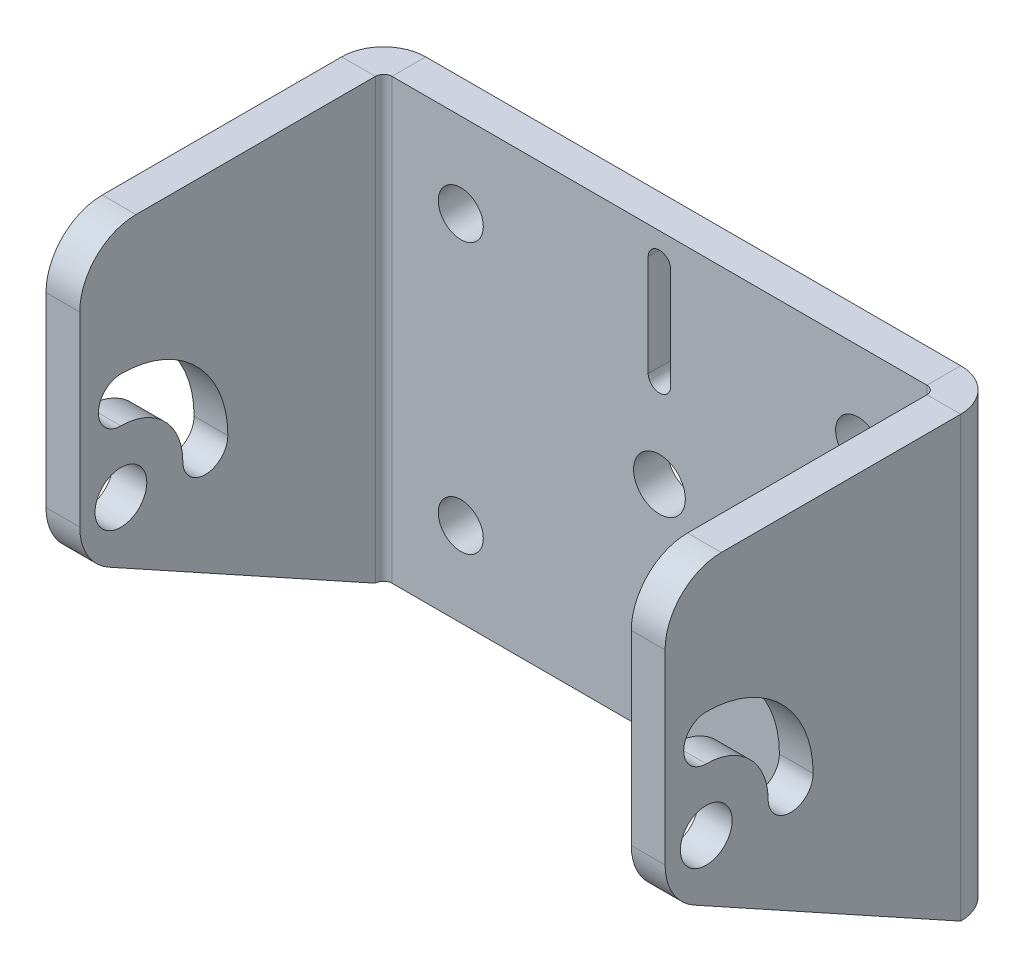
SolidWorks part; units mm, degrees
note: The reader was unsure of these and kept them because the rebuilt part matched: flange length of "Aresta-Flange1".
ref_plane "Plano frontal" through (0, 0, 0) normal (0, 0, 1) x (1, 0, 0)
ref_plane "Plano superior" through (0, 0, 0) normal (0, 1, 0) x (1, 0, 0)
ref_plane "Plano direito" through (0, 0, 0) normal (1, 0, 0) x (0, 0, -1)
sketch "Esboço1" plane through (0, 0, 0) normal (0, 0, 1) x (1, 0, 0)
  line L1 (-22.0063, 15.0091) -> (26.9937, 15.0091)
  line L2 (-22.0063, 15.0091) -> (-22.0063, -23.9909)
  line L3 (-22.0063, -23.9909) -> (26.9937, -23.9909)
  line L4 (26.9937, 15.0091) -> (26.9937, -23.9909)
  dimension "D1" = 49
  dimension "D2" = 39
base flange "Flange-base1" sketch "Esboço1" thickness 3 reverse thickness direction no parameters "D1"=0.7366
sketch "Esboço6" plane through (0, 0, 0) normal (0, 0, 1) x (1, 0, 0)
  line L1 (-15.1563, 7.5091) -> (20.1437, 7.5091)
  line L2 (-15.1563, 7.5091) -> (-15.1563, -16.4909)
  line L3 (-15.1563, -16.4909) -> (20.1437, -16.4909)
  line L4 (20.1437, 7.5091) -> (20.1437, -16.4909)
  line L6 (26.9937, 15.0091) -> (-22.0063, 15.0091) construction
  line L7 (-22.0063, -23.9909) -> (26.9937, -23.9909) construction
  line L8 (2.4937, 15.0091) -> (2.4937, -23.9909) construction
  line L9 (2.4937, 3.5238) -> (2.4937, 12.5238) construction
  line L10 (1.4937, 3.5238) -> (1.4937, 12.5238)
  line L11 (3.4937, 3.5238) -> (3.4937, 12.5238)
  line L12 (-22.0063, -4.4909) -> (26.9937, -4.4909) construction
  line L13 (-22.0063, 15.0091) -> (-22.0063, -23.9909) construction
  line L14 (26.9937, -23.9909) -> (26.9937, 15.0091) construction
  line L15 (2.4937, -12.5057) -> (2.4937, -21.5057) construction
  line L16 (1.4937, -12.5057) -> (1.4937, -21.5057)
  line L17 (3.4937, -12.5057) -> (3.4937, -21.5057)
  circle A0 centre (-15.1563, 7.5091) radius 2
  circle A1 centre (-15.1563, -16.4909) radius 2
  circle A2 centre (20.1437, -16.4909) radius 2
  circle A3 centre (20.1437, 7.5091) radius 2
  circle A4 centre (2.4937, -4.4909) radius 2.3
  arc A5 (1.4937, 3.5238) -> (3.4937, 3.5238) centre (2.4937, 3.5238) ccw
  arc A6 (3.4937, 12.5238) -> (1.4937, 12.5238) centre (2.4937, 12.5238) ccw
  arc A7 (1.4937, -12.5057) -> (3.4937, -12.5057) centre (2.4937, -12.5057) cw
  arc A8 (3.4937, -21.5057) -> (1.4937, -21.5057) centre (2.4937, -21.5057) cw
  point P18 (2.4937, 8.0238)
  point P31 (2.4937, -17.0057)
  dimension "D1" = 6.85
  dimension "D3" = 7.5
  dimension "D4" = 7.5
extrude "Corte-extrusão1" cut sketch "Esboço6" against normal blind 10 contours L1 A0 L2 | L2 A0 L1 | L2 A1 L3 | L3 A1 L2 | A4 | L10 A5 L11 L1 | L11 A6 L10 L1 | A7 L16 L3 L17 | A8 L17 L3 L16 | A2 L3 L4 | A2 L4 L3 | A3 L4 L1 | A3 L1 L4 normal cut yes
edge flange "Aresta-Flange1" sketch "Esboço11" flange profiles "Esboço11", "Esboço12" flange angle 90 flange length 30 flange position material outside bend radius 0.7366 thickness 3 parameters "D6"=10, "D8"=1
sketch "Esboço11" plane through (26.9937, 0, 0) normal (1, 0, 0) x (0, 1, 0)
  line L0 (-23.9909, 0) -> (15.0091, 0) construction
  line L1 (-23.9909, 0) -> (15.0091, 0)
  line L2 (-23.9909, 0) -> (-23.9909, 27)
  line L3 (-23.9909, 27) -> (15.0091, 27)
  line L4 (15.0091, 27) -> (15.0091, 0)
sketch "Esboço12" plane through (-22.0063, 0, 0) normal (-1, 0, 0) x (0, -1, 0)
  line L0 (-15.0091, 0) -> (23.9909, 0) construction
  line L1 (-15.0091, 0) -> (23.9909, 0)
  line L2 (-15.0091, 0) -> (-15.0091, 27)
  line L3 (-15.0091, 27) -> (23.9909, 27)
  line L4 (23.9909, 27) -> (23.9909, 0)
bend "DobradeAresta1" bend radius 0.7366 bend angle 90 parameters "D5"=1
bend "DobradeAresta2" bend radius 0.7366 bend angle 90 parameters "D5"=2
sketch "Esboço13" plane through (-25.0063, 0, 0) normal (-1, 0, 0) x (0, 0, 1)
  line L0 (0.7366, -23.9909) -> (27, -9.4909) construction
  line L1 (27, -23.9909) -> (27, 15.0091) construction
  line L2 (27, -9.4909) -> (0.7366, 15.0091) construction
  line L3 (0.7366, -23.9909) -> (27, -23.9909)
  line L4 (27, -23.9909) -> (27, -9.4909)
  line L5 (27, -9.4909) -> (0.7366, -23.9909)
  circle A0 centre (23.3439, -6.0803) radius 2.3
  arc A1 (23.3439, 1.4197) -> (15.8439, -6.0803) centre (23.3439, -6.0803) ccw construction
  arc A6 (23.3439, 3.4197) -> (13.8439, -6.0803) centre (23.3439, -6.0803) ccw
  arc A7 (23.3439, -0.5803) -> (17.8439, -6.0803) centre (23.3439, -6.0803) ccw
  arc A8 (23.3439, -0.5803) -> (23.3439, 3.4197) centre (23.3439, 1.4197) ccw
  arc A9 (13.8439, -6.0803) -> (17.8439, -6.0803) centre (15.8439, -6.0803) ccw
  point P12 (18.0406, -0.777)
  dimension "D3" = 4.6
  dimension "D4" = 3.6561
  dimension "D6" = 4
  dimension "D1" = 14.5
  dimension "D2" = 5
  dimension "D7" = 7.5
extrude "Corte-extrusão2" cut sketch "Esboço13" against normal blind 70 normal cut yes
fillet "Filete1" radius 5 4 edges at (28.4937, -9.4909, 27) (28.4937, 15.0091, 27) (-23.5063, -9.4909, 27) (-23.5063, 15.0091, 27)
sketch "Curva-Linhas1" [suppressed] plane through (0, 0, 0) normal (0, 1, 0) x (1, 0, 0)
sketch "Caixa delimitadora1" [suppressed] plane through (0, 0, 0) normal (0, 1, 0) x (1, 0, 0)
sheet metal parameters "Chapa metálica1" thickness 3 parameters "D1"=0.7366
flat pattern "Padrão-Plano1" [suppressed]
sketch "Curva-Linhas2" plane through (0, 0, 0) normal (0, 1, 0) x (1, 0, 0)
sketch3d "Caixa delimitadora2" [suppressed]
  line L0 (21.0063, -23.9909, 0) -> (-26.9937, -23.9909, 0) construction
  line L1 (21.0063, 15.0091, 0) -> (-26.9937, 15.0091, 0) construction
  line L2 (21.0063, -23.9909, 0) -> (21.0063, 15.0091, 0) construction
  line L3 (-26.9937, -23.9909, 0) -> (-26.9937, 15.0091, 0) construction
sheet metal parameters "Chapa metálica2" thickness 3 parameters "D1"=0.7366
flat pattern "Padrão-Plano1"
sketch "Curva-Linhas2" plane through (0, 0, 0) normal (0, 1, 0) x (1, 0, 0)
sketch3d "Caixa delimitadora2" [suppressed]
  line L0 (-21.0063, -23.9909, 0) -> (26.9937, -23.9909, 0) construction
  line L1 (-21.0063, 15.0091, 0) -> (26.9937, 15.0091, 0) construction
  line L2 (-21.0063, -23.9909, 0) -> (-21.0063, 15.0091, 0) construction
  line L3 (26.9937, -23.9909, 0) -> (26.9937, 15.0091, 0) construction
sheet metal parameters "Chapa metálica3" thickness 3 parameters "D1"=0.7366
flat pattern "Padrão-Plano1"
sketch "Curva-Linhas2" plane through (0, 0, 0) normal (0, 0, 1) x (1, 0, 0)
  line L0 (-22.0263, 15.0091) -> (-22.0263, -23.9909) construction
  line L1 (28.0138, -23.9909) -> (28.0138, 15.0091) construction
  line L2 (-22.0263, 15.0091) -> (-22.0263, -23.9909) construction
  line L3 (28.0138, -23.9909) -> (28.0138, 15.0091) construction
sketch3d "Caixa delimitadora2" [suppressed]
  line L0 (-50.0463, -23.9909, 0) -> (56.0338, -23.9909, 0) construction
  line L1 (-50.0463, 15.0091, 0) -> (56.0338, 15.0091, 0) construction
  line L2 (-50.0463, -23.9909, 0) -> (-50.0463, 15.0091, 0) construction
  line L3 (56.0338, -23.9909, 0) -> (56.0338, 15.0091, 0) construction
bend of the flat pattern "Planificar-<DobradeAresta1>1"
bend of the flat pattern "Planificar-<DobradeAresta2>1"
sheet metal parameters "Chapa metálica4" thickness 3 parameters "D1"=0.7366
flat pattern "Padrão-Plano1"
sketch "Curva-Linhas2" plane through (0, 0, 0) normal (0, 0, 1) x (1, 0, 0)
  line L0 (-23.0263, 15.0091) -> (-23.0263, -23.9909) construction
  line L1 (28.0138, -23.9909) -> (28.0138, 15.0091) construction
  line L2 (-23.0263, 15.0091) -> (-23.0263, -23.9909) construction
  line L3 (28.0138, -23.9909) -> (28.0138, 15.0091) construction
sketch3d "Caixa delimitadora2" [suppressed]
  line L0 (-51.0463, -23.9909, 0) -> (56.0338, -23.9909, 0) construction
  line L1 (-51.0463, 15.0091, 0) -> (56.0338, 15.0091, 0) construction
  line L2 (-51.0463, -23.9909, 0) -> (-51.0463, 15.0091, 0) construction
  line L3 (56.0338, -23.9909, 0) -> (56.0338, 15.0091, 0) construction
bend of the flat pattern "Planificar-<DobradeAresta1>1"
bend of the flat pattern "Planificar-<DobradeAresta2>1"
